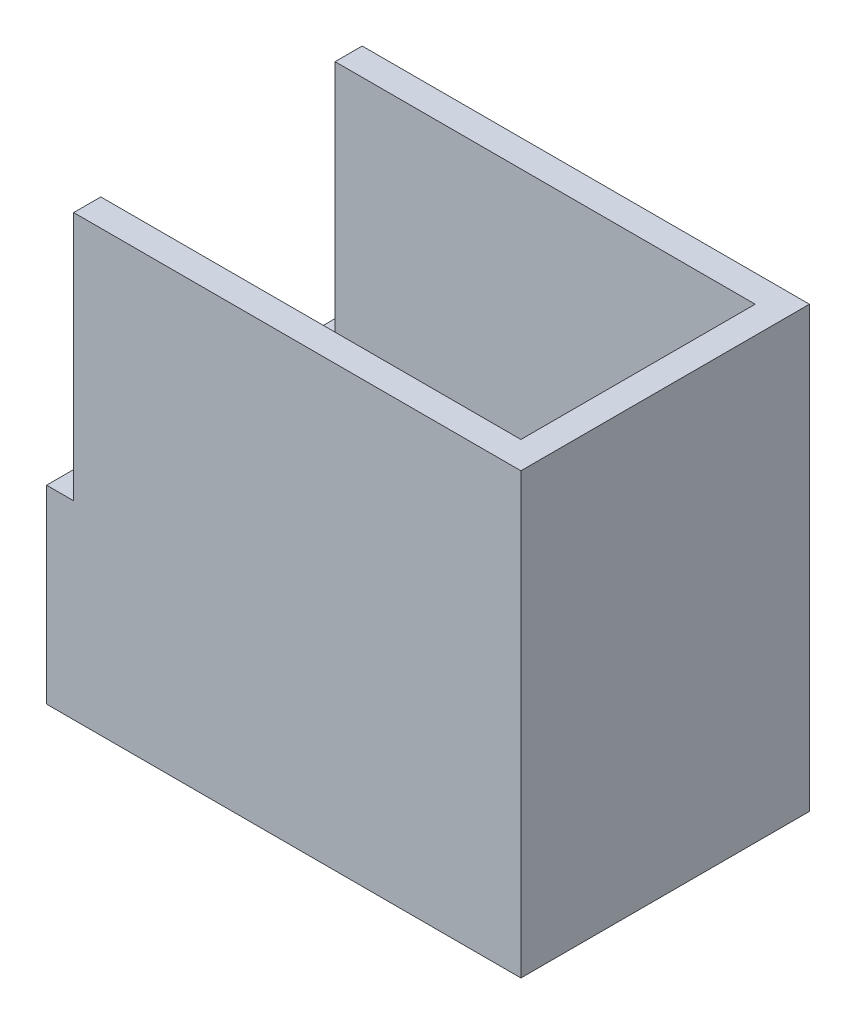
SolidWorks part; units mm, degrees
material "ABS"
ref_plane "前视基准面" through (0, 0, 0) normal (0, 0, 1) x (1, 0, 0)
ref_plane "上视基准面" through (0, 0, 0) normal (0, 1, 0) x (1, 0, 0)
ref_plane "右视基准面" through (0, 0, 0) normal (1, 0, 0) x (0, 0, -1)
other "Configuration Table"
sketch "草图13" plane through (0, 0, 0) normal (0, 1, 0) x (1, 0, 0)
  line L0 (-11.62, 6.48) -> (-11.62, -6.48)
  line L1 (-11.22, 6.08) -> (11.22, 6.08) construction
  line L2 (-11.22, 6.08) -> (-11.22, -6.08) construction
  line L3 (-11.22, -6.08) -> (11.22, -6.08) construction
  line L4 (11.22, 6.08) -> (11.22, -6.08) construction
  line L5 (-11.22, 6.08) -> (11.22, -6.08) construction
  line L6 (-11.22, -6.08) -> (11.22, 6.08) construction
  line L7 (-11.62, -6.48) -> (11.62, -6.48)
  line L8 (11.62, 6.48) -> (11.62, -6.48)
  line L9 (-11.62, 6.48) -> (11.62, 6.48)
  line L10 (-13.12, 7.98) -> (-13.12, -7.98)
  line L11 (-13.12, -7.98) -> (13.12, -7.98)
  line L12 (13.12, 7.98) -> (13.12, -7.98)
  line L13 (-13.12, 7.98) -> (13.12, 7.98)
  line L14 (-9.7, 6.48) -> (-9.7, -6.48)
  line L15 (-9.3, 6.08) -> (-6.78, 6.08) construction
  line L16 (-9.3, 6.08) -> (-9.3, -6.08) construction
  line L17 (-9.3, -6.08) -> (-6.78, -6.08) construction
  line L18 (-6.78, 6.08) -> (-6.78, -6.08) construction
  line L19 (-9.7, -6.48) -> (-6.38, -6.48)
  line L20 (-6.38, 6.48) -> (-6.38, -6.48)
  line L21 (-9.7, 6.48) -> (-6.38, 6.48)
  point P0 (0, 0)
  point P18 (-41.9648, 1.2573)
  dimension "D1" = 12.16
  dimension "D2" = 22.44
  dimension "D6" = 18
  dimension "D7" = 2.52
  dimension "D3" = 0.4
  dimension "D4" = 1.5
  dimension "D5" = 0.4
extrude "凸台-拉伸1" add sketch "草图13" along normal blind 22.8 contours L10 L11 L12 L13 | L0 L7 L8 L9
extrude "凸台-拉伸2" add sketch "草图13<3>" against normal blind 1.5 contours L14 L9 L0 L7 | L9 L20 L7 L8 | L13 L10 L11 L12 L0 L9 L8 L7 region at (-10.66, 0, 0) region at (2.62, 0, 0) region at (0, 0, -7.6729)
sketch "草图13<3>" plane through (0, 0, 0) normal (0, 1, 0) x (1, 0, 0) same geometry as "草图13"
sketch "草图15" plane through (-13.12, 0, 0) normal (-1, 0, 0) x (0, 0, 1)
  line L0 (7.98, 22.8) -> (7.98, -1.5) construction
  line L1 (-7.98, 7.74) -> (7.98, 7.74)
  line L2 (-7.98, 7.74) -> (-7.98, 22.8)
  line L3 (-7.98, 22.8) -> (7.98, 22.8)
  line L4 (7.98, 7.74) -> (7.98, 22.8)
  line L5 (-7.98, 7.74) -> (7.98, 22.8) construction
  line L6 (-7.98, 22.8) -> (7.98, 7.74) construction
  line L7 (-7.98, 22.8) -> (7.98, 22.8) construction
  line L8 (-7.98, 8.99) -> (7.98, 8.99)
  line L9 (-7.98, 22.8) -> (-7.98, -1.5) construction
  circle A0 centre (0, 9.39) radius 1.65
  point P0 (0, 15.27)
  point P12 (0, 0)
  point P15 (0, 0)
  point P16 (0, 0)
  line M7 (-7.98, 22.8) -> (-7.98, -1.5)
  line M10 (7.98, 22.8) -> (-7.98, 22.8)
  dimension "D2" = 3.3
  dimension "D1" = 7.74
  dimension "D3" = 0.4
extrude "切除-拉伸4" cut sketch "草图15" against normal up to surface (1.5 mm away) contours L8 A0 | L8 A0 | A0 L8 L4 M10 M7 region at (-13.12, 8.4691, 0) region at (-13.12, 16.0513, 0) region at (-13.12, 9.8798, 0) up to face at (-11.62, 11.4, 0)
